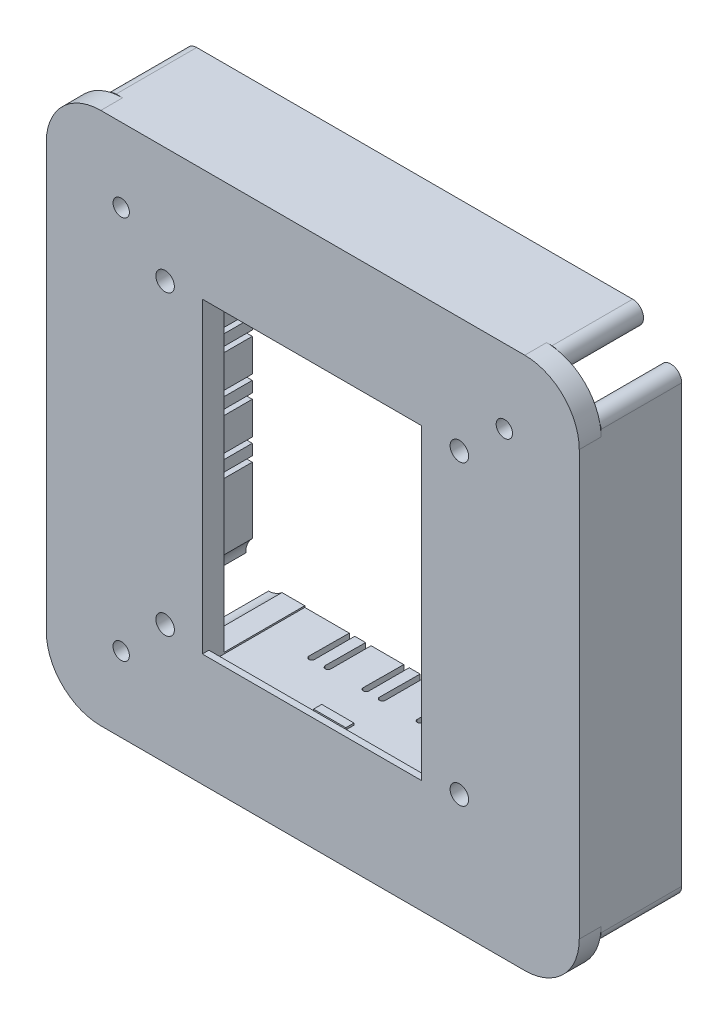
SolidWorks part; units mm, degrees
ref_plane "Front Plane" through (0, 0, 0) normal (0, 0, 1) x (1, 0, 0)
ref_plane "Top Plane" through (0, 0, 0) normal (0, 1, 0) x (1, 0, 0)
ref_plane "Right Plane" through (0, 0, 0) normal (1, 0, 0) x (0, 0, -1)
sketch "Sketch1" plane through (0, 0, 0) normal (0, 0, 1) x (1, 0, 0)
  line L0 (-0.2, 90) -> (-0.2, 10)
  line L1 (-89.8, 100) -> (-10, 100)
  line L2 (-99.8, 90) -> (-99.8, 10)
  line L3 (-89.8, 0) -> (-10, 0)
  line L4 (0, 90) -> (0, 10)
  line L5 (-89.8, 99.8) -> (-10, 99.8)
  line L6 (-99.6, 90) -> (-99.6, 10)
  line L7 (-89.8, 0.2) -> (-10, 0.2)
  arc A0 (-99.8, 10) -> (-89.8, 0) centre (-89.8, 10) ccw
  arc A1 (-10, 0) -> (0, 10) centre (-10, 10) ccw
  arc A2 (-10, 100) -> (0, 90) centre (-10, 90) cw
  arc A3 (-89.8, 100) -> (-99.8, 90) centre (-89.8, 90) ccw
  arc A4 (-10, 0.2) -> (-0.2, 10) centre (-10, 10) ccw
  arc A5 (-10, 99.8) -> (-0.2, 90) centre (-10, 90) cw
  arc A6 (-89.8, 99.8) -> (-99.6, 90) centre (-89.8, 90) ccw
  arc A7 (-99.6, 10) -> (-89.8, 0.2) centre (-89.8, 10) ccw
  point P9 (0, 0)
  dimension "D1" = 10
  dimension "D2" = 0.2
extrude "Boss-Extrude1" add sketch "Sketch1" along normal blind 4 contours L6 A7 L7 A4 L0 A5 L5 A6 | A4 L0 A5 L5 A6 L6 A7 L7 region at (-49.9, 50, 0)
sketch "Sketch2" plane through (0, 0, 0) normal (0, 0, -1) x (-1, 0, 0)
  line L0 (3, 90) -> (18, 75)
  line L1 (18, 75) -> (18, 25)
  line L2 (18, 75) -> (18, 25) construction
  line L3 (3, 90) -> (3, 10)
  line L4 (3, 10) -> (3, 90) construction
  line L5 (18, 50) -> (0.2, 50) construction
  line L6 (0.2, 90) -> (0.2, 10) construction
  line L7 (49.9, 99.8) -> (49.9, 57.945) construction
  line L8 (89.8, 99.8) -> (10, 99.8) construction
  line L9 (3, 10) -> (18, 25)
  line L10 (3, 90) -> (18, 75)
  line L11 (3, 10) -> (18, 25)
  line L12 (3, 90) -> (18, 75)
  line L13 (3, 10) -> (18, 25)
  line L14 (3, 90) -> (18, 75)
  line L15 (3, 10) -> (18, 25)
  line L16 (3, 90) -> (18, 75)
  line L17 (3, 10) -> (18, 25)
  line L18 (3, 90) -> (18, 75)
  line L19 (3, 10) -> (18, 25)
  line L20 (3, 90) -> (18, 75)
  line L21 (3, 10) -> (18, 25)
  line L22 (3, 90) -> (18, 75)
  line L23 (3, 10) -> (18, 25)
  line L24 (96.8, 90) -> (81.8, 75)
  line L25 (81.8, 75) -> (81.8, 25)
  line L26 (96.8, 10) -> (81.8, 25)
  line L27 (96.8, 90) -> (96.8, 10)
  line L28 (3.0704, 3.0704) -> (97.0711, 97.0711) construction
  line L29 (90, 3) -> (75, 18)
  line L30 (75, 18) -> (25, 18)
  line L31 (10, 3) -> (25, 18)
  line L32 (90, 3) -> (10, 3)
  line L33 (90, 96.8) -> (10, 96.8)
  line L34 (10, 96.8) -> (25, 81.8)
  line L35 (75, 81.8) -> (25, 81.8)
  line L36 (90, 96.8) -> (75, 81.8)
  line L37 (1, 90) -> (1, 10)
  line L38 (4.4142, 8.5858) -> (19.4142, 23.5858)
  line L39 (20, 75) -> (20, 25)
  line L40 (4.4142, 91.4142) -> (19.4142, 76.4142)
  line L41 (90, 98.8) -> (10, 98.8)
  line L42 (8.5858, 95.3858) -> (23.5858, 80.3858)
  line L43 (75, 79.8) -> (25, 79.8)
  line L44 (91.4142, 95.3858) -> (76.4142, 80.3858)
  line L45 (95.3858, 91.4142) -> (80.3858, 76.4142)
  line L46 (79.8, 75) -> (79.8, 25)
  line L47 (95.3858, 8.5858) -> (80.3858, 23.5858)
  line L48 (98.8, 90) -> (98.8, 10)
  line L49 (91.4142, 4.4142) -> (76.4142, 19.4142)
  line L50 (75, 20) -> (25, 20)
  line L51 (8.5858, 4.4142) -> (23.5858, 19.4142)
  line L52 (90, 1) -> (10, 1)
  line L53 (1, 5.1716) -> (20, 24.1716) construction
  line L54 (20, 75.8284) -> (20, 24.1716) construction
  line L55 (75.8284, 20) -> (24.1716, 20) construction
  line L56 (5.1716, 1) -> (24.1716, 20) construction
  line L57 (94.8284, 1) -> (75.8284, 20) construction
  line L58 (79.8, 75.8284) -> (79.8, 24.1716) construction
  line L59 (98.8, 5.1716) -> (79.8, 24.1716) construction
  line L60 (98.8, 94.8284) -> (79.8, 75.8284) construction
  line L61 (75.8284, 79.8) -> (24.1716, 79.8) construction
  line L62 (94.8284, 98.8) -> (75.8284, 79.8) construction
  line L63 (5.1716, 98.8) -> (24.1716, 79.8) construction
  line L64 (1, 94.8284) -> (20, 75.8284) construction
  line L65 (94.8284, 98.8) -> (5.1716, 98.8) construction
  line L66 (1, 94.8284) -> (1, 5.1716) construction
  line L67 (94.8284, 1) -> (5.1716, 1) construction
  line L68 (98.8, 94.8284) -> (98.8, 5.1716) construction
  arc A0 (0.2, 10) -> (10, 0.2) centre (10, 10) ccw construction
  arc A1 (100, 90) -> (90, 100) centre (90, 90) ccw construction
  arc A2 (19.4142, 23.5858) -> (20, 25) centre (18, 25) ccw
  arc A3 (25, 20) -> (23.5858, 19.4142) centre (25, 18) ccw
  arc A4 (76.4142, 19.4142) -> (75, 20) centre (75, 18) ccw
  arc A5 (79.8, 25) -> (80.3858, 23.5858) centre (81.8, 25) ccw
  arc A6 (80.3858, 76.4142) -> (79.8, 75) centre (81.8, 75) ccw
  arc A7 (75, 79.8) -> (76.4142, 80.3858) centre (75, 81.8) ccw
  arc A8 (23.5858, 80.3858) -> (25, 79.8) centre (25, 81.8) ccw
  arc A9 (20, 75) -> (19.4142, 76.4142) centre (18, 75) ccw
  arc A10 (10, 98.8) -> (8.5858, 95.3858) centre (10, 96.8) ccw
  arc A11 (1, 90) -> (4.4142, 91.4142) centre (3, 90) cw
  arc A12 (1, 10) -> (4.4142, 8.5858) centre (3, 10) ccw
  arc A13 (8.5858, 4.4142) -> (10, 1) centre (10, 3) ccw
  arc A14 (91.4142, 4.4142) -> (90, 1) centre (90, 3) cw
  arc A15 (95.3858, 8.5858) -> (98.8, 10) centre (96.8, 10) ccw
  arc A16 (95.3858, 91.4142) -> (98.8, 90) centre (96.8, 90) cw
  arc A17 (90, 98.8) -> (91.4142, 95.3858) centre (90, 96.8) cw
  point P18 (3, 50)
  dimension "D2" = 2
  dimension "D1" = 2
extrude "Boss-Extrude2" add sketch "Sketch2" along normal blind 14.8 contours L37 A12 L38 A2 L39 A9 L40 A11 L9 L3 L0 L1 | A14 L49 A4 L50 A3 L51 A13 L52 L29 L32 L31 L30 | A16 L45 A6 L46 A5 L47 A15 L48 L24 L27 L26 L25 | A17 L41 A10 L42 A8 L43 A7 L44 L33 L36 L35 L34 region at (-2.5642, 91.0521, 0) region at (-91.0521, 97.2358, 0) region at (-97.2358, 91.0521, 0) region at (-91.0521, 2.5642, 0)
sketch "Sketch4" plane through (0, 0, 0) normal (0, 0, -1) x (-1, 0, 0)
  line L0 (3.0704, 3.0704) -> (97.0711, 97.0711) construction
  line L1 (3.0704, 96.9296) -> (97.0711, 2.9289) construction
  line L2 (50.0707, 49.9293) -> (70.1707, 49.9293)
  line L3 (50.0707, 49.9293) -> (50.0707, 19.7293)
  line L4 (29.9707, 19.7293) -> (70.1707, 19.7293)
  line L5 (70.1707, 19.7293) -> (70.1707, 80.1293)
  line L6 (29.9707, 19.7293) -> (29.9707, 80.1293)
  line L7 (29.9707, 80.1293) -> (70.1707, 80.1293)
  arc A0 (0.2, 10) -> (10, 0.2) centre (10, 10) ccw construction
  arc A1 (100, 90) -> (90, 100) centre (90, 90) ccw construction
  arc A2 (10, 99.8) -> (0.2, 90) centre (10, 90) ccw construction
  arc A3 (90, 0) -> (100, 10) centre (90, 10) ccw construction
  point P23 (29.9707, 49.9293)
  dimension "D1" = 60.4
  dimension "D2" = 40.2
extrude "Cut-Extrude1" cut sketch "Sketch4" against normal blind 14.8 and the other way blind 21.8 contours L4 L5 L2 L3 | L7 L6 L4 L3 L2 L5 region at (-46.7207, 54.9626, 0) region at (-60.1207, 34.8293, 0)
sketch "Sketch5" plane through (-20, 0, 0) normal (-1, 0, 0) x (0, 0, 1)
  line L0 (-14.8, 50) -> (0, 50) construction
  line L1 (-14.8, 90) -> (-14.8, 10) construction
  line L2 (0, 90) -> (0, 10) construction
  line L3 (-7.4, 50) -> (-7.4, 90) construction
  line L4 (-14.8, 90) -> (0, 90) construction
  line L5 (-7.4, 50) -> (-7.4, 10) construction
  line L6 (-14.8, 10) -> (0, 10) construction
  line L7 (-7.4, 30) -> (-14.8, 30) construction
  line L8 (-7.4, 70) -> (-14.8, 70) construction
sketch "Sketch6" plane through (0, 80.1293, 0) normal (0, -1, 0) x (1, 0, 0)
  line L0 (-29.9707, 4) -> (-70.1707, 4)
  line L1 (-29.9707, 4) -> (-70.1707, 4) construction
  line L2 (-29.9707, 4) -> (-29.9707, 2.8)
  line L3 (-29.9707, 2.8) -> (-70.1707, 2.8)
  line L4 (-70.1707, 2.8) -> (-70.1707, 4)
  dimension "D1" = 1.2
extrude "Boss-Extrude3" add sketch "Sketch6" along normal blind 2
sketch "Sketch7" plane through (0, 19.7293, 0) normal (0, 1, 0) x (1, 0, 0)
  line L0 (-29.9707, 14.8) -> (-29.9707, -4) construction
  line L1 (-70.1707, -4) -> (-29.9707, -4)
  line L2 (-70.1707, -4) -> (-70.1707, -2.8)
  line L3 (-70.1707, -2.8) -> (-29.9707, -2.8)
  line L4 (-29.9707, -4) -> (-29.9707, -2.8)
  dimension "D1" = 1.2
extrude "Boss-Extrude4" add sketch "Sketch7" along normal blind 2
sketch "Sketch8" plane through (0, 19.7293, 0) normal (0, 1, 0) x (1, 0, 0)
  line L0 (-49.9, -4) -> (-49.9, -0.9) construction
  line L1 (-89.8, -4) -> (-10, -4) construction
  line L2 (-46.9368, -0.9) -> (-46.9368, 0.6)
  line L3 (-52.8632, -0.9) -> (-46.9368, -0.9)
  line L4 (-52.8632, -0.9) -> (-52.8632, 0.6)
  line L5 (-52.8632, 0.6) -> (-46.9368, 0.6)
  line L6 (-49.9, -0.9) -> (-49.9, 0.6) construction
  dimension "D1" = 3.1
  dimension "D2" = 1.5
extrude "Boss-Extrude5" add sketch "Sketch8" along normal blind 0.35
ref_plane "Plane1" through (0, 50, 0) normal (0, -1, 0) x (-1, 0, 0)
sketch "Sketch9" plane through (0, 0, 0) normal (0, 0, -1) x (-1, 0, 0)
  circle A0 centre (23, 77.5728) radius 4
  circle A1 centre (23, 23) radius 4
  circle A2 centre (77, 23) radius 4
  circle A3 centre (77, 77.5728) radius 4
extrude "Cut-Extrude2" cut sketch "Sketch9" along normal blind 22.15
sketch "Sketch10" plane through (0, 0, 4) normal (0, 0, 1) x (1, 0, 0)
  line L0 (-3.0704, 3.0704) -> (-96.7296, 96.9296) construction
  line L1 (-3.0704, 96.9296) -> (-96.7835, 3.2165) construction
  line L2 (-49.9, 50) -> (-49.9, 82.409) construction
  line L3 (-49.9, 50) -> (-83.7524, 50) construction
  arc A0 (-10, 0.2) -> (-0.2, 10) centre (-10, 10) ccw construction
  arc A1 (-89.8, 99.8) -> (-99.6, 90) centre (-89.8, 90) ccw construction
  arc A4 (-0.2, 90) -> (-10, 99.8) centre (-10, 90) ccw construction
  circle A5 centre (-85.0551, 85.2302) radius 1.5
  circle A6 centre (-85.0551, 14.7698) radius 1.5
  circle A7 centre (-14.7449, 85.2302) radius 1.5
extrude "Cut-Extrude3" cut sketch "Sketch10" against normal blind 6.15
sketch "Sketch11" plane through (0, 0, 0) normal (0, 0, -1) x (-1, 0, 0)
  circle A0 centre (77, 77.5728) radius 1.7
  circle A1 centre (77, 23) radius 1.7
  circle A2 centre (23, 23) radius 1.7
  circle A3 centre (23, 77.5728) radius 1.7
extrude "Cut-Extrude4" cut sketch "Sketch11" against normal blind 60
sketch "Sketch12" plane through (0, 0, 0) normal (0, 0, -1) x (-1, 0, 0)
  line L0 (11, 98.8) -> (88.8, 98.8)
  line L1 (98.8, 88.8) -> (98.8, 11)
  line L2 (88.8, 1) -> (11, 1)
  line L3 (1, 11) -> (1, 88.8)
  line L5 (-3.9703, 102.9022) -> (105.0317, 102.9022)
  line L6 (-3.9703, 102.9022) -> (-3.9703, -3.037)
  line L7 (-3.9703, -3.037) -> (105.0317, -3.037)
  line L8 (105.0317, 102.9022) -> (105.0317, -3.037)
  arc A4 (11, 1) -> (1, 11) centre (11, 11) cw
  arc A5 (88.8, 1) -> (98.8, 11) centre (88.8, 11) ccw
  arc A6 (98.8, 88.8) -> (88.8, 98.8) centre (88.8, 88.8) ccw
  arc A7 (1, 88.8) -> (11, 98.8) centre (11, 88.8) cw
  dimension "D1" = 10
extrude "Cut-Extrude5" cut sketch "Sketch12" against normal blind 60
sketch "Sketch13" plane through (-18, 0, 0) normal (1, 0, 0) x (0, 0, -1)
  line L0 (14.8, 75) -> (14.8, 25) construction
  line L1 (14.8, 25) -> (0, 25) construction
  line L2 (0, 25) -> (0, 75) construction
  line L3 (0, 75) -> (14.8, 75) construction
  line L4 (0, 50) -> (14.8, 50) construction
  line L5 (7.4, 50) -> (7.4, 51.5) construction
  line L6 (7.4, 50) -> (7.4, 48.5) construction
  line L7 (7.4, 51) -> (14.8, 51)
  line L8 (7.4, 49) -> (14.8, 49)
  line L9 (7.4, 48) -> (14.8, 48)
  line L10 (7.4, 52) -> (14.8, 52)
  line L11 (14.8, 52) -> (14.8, 51)
  line L12 (14.8, 49) -> (14.8, 48)
  line L13 (7.4, 61) -> (14.8, 61)
  line L14 (7.4, 59) -> (14.8, 59)
  line L15 (7.4, 58) -> (14.8, 58)
  line L16 (7.4, 62) -> (14.8, 62)
  line L17 (14.8, 62) -> (14.8, 61)
  line L18 (14.8, 59) -> (14.8, 58)
  line L19 (14.8, 85) -> (14.8, 35) construction
  line L20 (0, 60) -> (14.8, 60) construction
  line L21 (7.4, 60) -> (7.4, 61.5) construction
  line L22 (7.4, 60) -> (7.4, 58.5) construction
  line L23 (7.4, 40) -> (7.4, 41.5) construction
  line L24 (7.4, 40) -> (7.4, 38.5) construction
  line L25 (0, 40) -> (14.8, 40) construction
  line L26 (14.8, 15) -> (14.8, 65) construction
  line L27 (14.8, 41) -> (14.8, 42)
  line L28 (14.8, 38) -> (14.8, 39)
  line L29 (7.4, 38) -> (14.8, 38)
  line L30 (7.4, 42) -> (14.8, 42)
  line L31 (7.4, 41) -> (14.8, 41)
  line L32 (7.4, 39) -> (14.8, 39)
  line L33 (14.8, 42) -> (14.8, 38)
  line L34 (14.8, 62) -> (14.8, 58)
  circle A0 centre (7.4, 50) radius 3
  circle A1 centre (7.4, 51.5) radius 0.5
  circle A2 centre (7.4, 48.5) radius 0.5
  circle A3 centre (7.4, 60) radius 3
  circle A4 centre (7.4, 61.5) radius 0.5
  circle A5 centre (7.4, 58.5) radius 0.5
  circle A6 centre (7.4, 41.5) radius 0.5
  circle A7 centre (7.4, 38.5) radius 0.5
  circle A8 centre (7.4, 40) radius 3
  line M4 (14.8, 25) -> (14.8, 75)
  dimension "D1" = 2
extrude "Cut-Extrude6" cut sketch "Sketch13" against normal blind 8 contours A0 L7 L10 M4 | A0 L9 L8 M4 | A3 L15 L14 M4 | A3 L13 L16 M4 | L30 A8 L31 M4 | L32 A8 L29 M4 | A8 L32 A7 L29 | A8 L30 A6 L31 | A6 | A2 | A2 L9 A0 L8 | A1 L7 A0 L10 | A1 | A5 | A5 L15 A3 L14 | A4 | A4 L13 A3 L16 | A7 region at (-18, 51.4776, -8.8883) region at (-18, 51.5, -7.4) region at (-18, 51.5101, -12.3852) region at (-18, 41.5101, -12.3852) region at (-18, 58.4899, -12.3852) region at (-18, 48.4899, -12.3852) region at (-18, 48.5224, -8.8883) region at (-18, 48.5, -7.4) region at (-18, 58.5224, -8.8883) region at (-18, 58.5, -7.4) region at (-18, 61.4776, -8.8883) region at (-18, 61.5101, -12.3852) region at (-18, 41.4776, -8.8883) region at (-18, 61.5, -7.4) region at (-18, 38.4899, -12.3852) region at (-18, 41.5, -7.4) region at (-18, 38.5224, -8.8883)
extrude "Cut-Extrude7" cut sketch "Sketch13<4>" against normal blind 0.5 contours A2 L8 A0 L7 A1 L10 L9 | A8 | A3 region at (-18, 50, -7.109)
sketch "Sketch13<4>" plane through (-18, 0, 0) normal (1, 0, 0) x (0, 0, -1) same geometry as "Sketch13"
sketch "Sketch14" plane through (0, 0, 0) normal (0, 0, -1) x (-1, 0, 0)
  line L0 (3.3431, 96.4569) -> (95.8711, 95.8711) construction
  line L1 (3.3431, 3.3431) -> (96.4569, 96.4569) construction
  arc A1 (98.5705, 90.9303) -> (90.9303, 98.5705) centre (88.8, 88.8) ccw construction
ref_plane "Plane3" through (0, 0, 0) normal (-0.7071, -0.7071, 0) x (-0.7071, 0.7071, 0)
mirror "Mirror2" about plane through (0, 0, 0) normal (-0.7071, -0.7071, 0) of "Cut-Extrude7", "Cut-Extrude6"
ref_plane "Plane4" through (-50.0587, 0, -0.2011) normal (1, 0, 0.004) x (0.004, 0, -1)
ref_plane "Plane5" through (0, 50, 0) normal (0, -1, 0) x (-1, 0, 0)
mirror "Mirror3" about plane through (-50.0587, 0, -0.2011) normal (1, 0, 0.004) of "Mirror2" second plane through (0, 50, 0) second plane normal (0, -1, 0)
